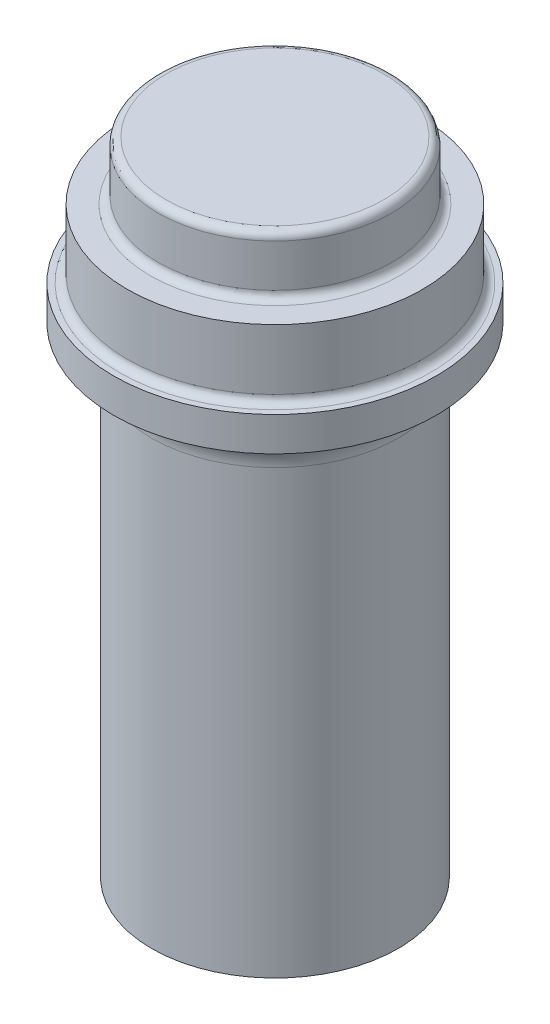
SolidWorks part; units mm, degrees
ref_plane "Front" through (0, 0, 0) normal (0, 0, 1) x (1, 0, 0)
ref_plane "Top" through (0, 0, 0) normal (0, 1, 0) x (1, 0, 0)
ref_plane "Right" through (0, 0, 0) normal (1, 0, 0) x (0, 0, -1)
sketch "Sketch1" plane through (0, 0, 0) normal (0, 1, 0) x (1, 0, 0)
  circle A0 centre (0, 0) radius 15.9
  dimension "D1" = 31.8
extrude "Boss-Extrude1" add sketch "Sketch1" along normal blind 62 contours A0
sketch "Sketch2" plane through (0, 62, 0) normal (0, 1, 0) x (1, 0, 0)
  circle A0 centre (0, 0) radius 20.8
  dimension "D1" = 41.6
extrude "Boss-Extrude2" add sketch "Sketch2" along normal blind 4.4
sketch "Sketch3" plane through (0, 66.4, 0) normal (0, 1, 0) x (1, 0, 0)
  circle A0 centre (0, 0) radius 19.05
  dimension "D1" = 38.1
extrude "Boss-Extrude3" add sketch "Sketch3" along normal blind 8.8
sketch "Sketch4" plane through (0, 75.2, 0) normal (0, 1, 0) x (1, 0, 0)
  circle A0 centre (0, 0) radius 15.05
  dimension "D1" = 30.1
extrude "Boss-Extrude4" add sketch "Sketch4" along normal blind 7.5
fillet "Fillet1" radius 5 1 edges at (0, 62, 15.9)
fillet "Fillet2" radius 1 3 edges at (0, 82.7, 15.05) (0, 75.2, 15.05) (0, 66.4, 19.05)
